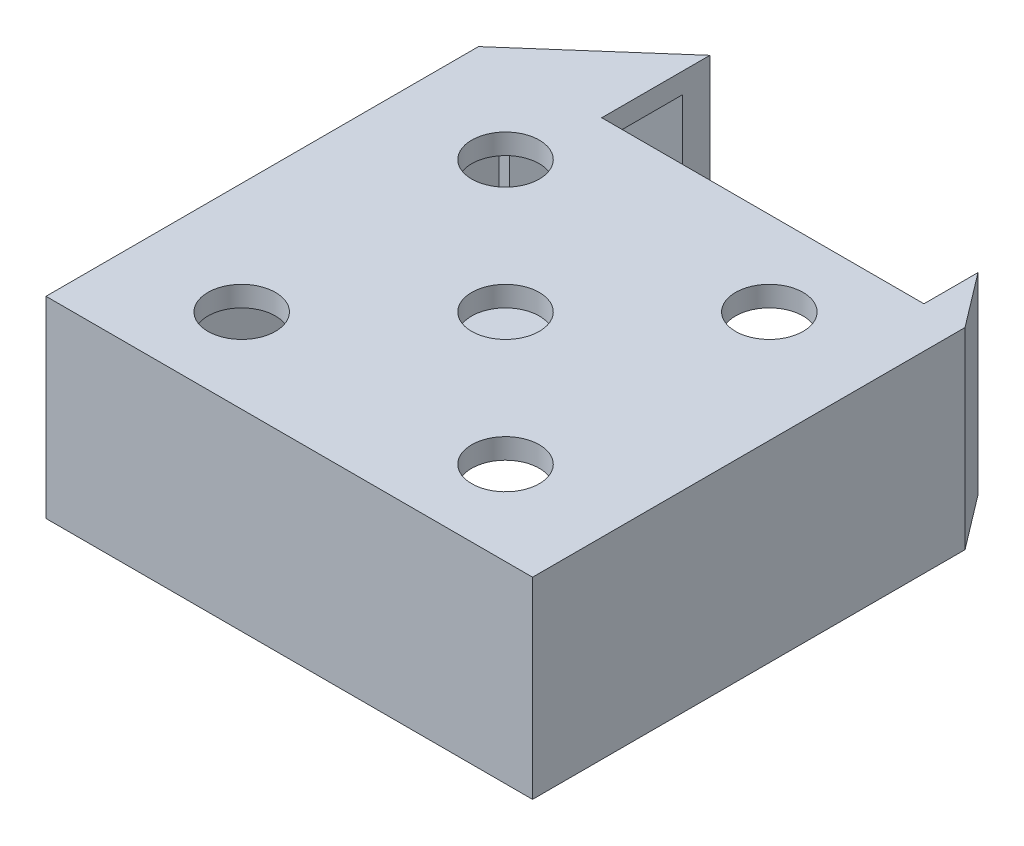
SolidWorks part; units mm, degrees
ref_plane "Front Plane" through (0, 0, 0) normal (0, 0, 1) x (1, 0, 0)
ref_plane "Top Plane" through (0, 0, 0) normal (0, 1, 0) x (1, 0, 0)
ref_plane "Right Plane" through (0, 0, 0) normal (1, 0, 0) x (0, 0, -1)
sketch "Sketch1" plane through (0, 0, 0) normal (0, 1, 0) x (1, 0, 0)
  line L1 (-28.575, 25.4) -> (28.575, 25.4)
  line L2 (-28.575, 25.4) -> (-28.575, -25.4)
  line L3 (-28.575, -25.4) -> (28.575, -25.4)
  line L4 (28.575, 25.4) -> (28.575, -25.4)
  point P4 (0, -25.4)
  point P6 (-28.575, 0)
  dimension "D1" = 57.15
  dimension "D2" = 50.8
extrude "Boss-Extrude1" add sketch "Sketch1" along normal mid plane 22.606
sketch "Sketch2" plane through (0, 0, -25.4) normal (0, 0, -1) x (-1, 0, 0)
  line L0 (-28.575, 11.303) -> (28.575, 11.303) construction
  line L1 (-26.175, 8.903) -> (26.175, 8.903)
  line L2 (-26.175, 8.903) -> (-26.175, -8.903)
  line L3 (-26.175, -8.903) -> (26.175, -8.903)
  line L4 (26.175, 8.903) -> (26.175, -8.903)
  line L5 (-28.575, 11.303) -> (-28.575, -11.303) construction
  point P4 (0, -8.903)
  point P6 (-26.175, 0)
  dimension "D1" = 2.4
  dimension "D2" = 2.4
extrude "Cut-Extrude1" cut sketch "Sketch2" against normal offset from surface (48.514 mm away) 2.286 up to face at (0, 0, 25.4)
sketch "Sketch3" plane through (0, -11.303, 0) normal (0, -1, 0) x (1, 0, 0)
  line L1 (15.494, -15.494) -> (-15.494, -15.494) construction
  line L2 (15.494, -15.494) -> (15.494, 15.494) construction
  line L3 (15.494, 15.494) -> (-15.494, 15.494) construction
  line L4 (-15.494, -15.494) -> (-15.494, 15.494) construction
  line L5 (15.494, -15.494) -> (-15.494, 15.494) construction
  line L6 (15.494, 15.494) -> (-15.494, -15.494) construction
  circle A0 centre (-15.494, 15.494) radius 2.032
  circle A1 centre (15.494, 15.494) radius 2.032
  circle A2 centre (15.494, -15.494) radius 2.032
  circle A3 centre (-15.494, -15.494) radius 2.032
  circle A4 centre (0, 0) radius 11.1125
  point P0 (0, 0)
  point P6 (0, 15.494)
  point P7 (-15.494, 0)
  dimension "D2" = 4.064
  dimension "D3" = 22.225
  dimension "D1" = 30.988
extrude "Cut-Extrude2" cut sketch "Sketch3" against normal up to surface (2.4 mm away) up to face at (0, -8.903, -1.143)
sketch "Sketch4" plane through (0, 11.303, 0) normal (0, 1, 0) x (1, 0, 0)
  circle A0 centre (-15.494, -15.494) radius 2.032 construction
  circle A1 centre (-15.494, 15.494) radius 2.032 construction
  circle A2 centre (15.494, 15.494) radius 2.032 construction
  circle A3 centre (15.494, -15.494) radius 2.032 construction
  circle A4 centre (-15.494, -15.494) radius 2.032 construction
  circle A5 centre (-15.494, 15.494) radius 2.032 construction
  circle A6 centre (15.494, 15.494) radius 2.032 construction
  circle A7 centre (15.494, -15.494) radius 2.032 construction
  circle A8 centre (-15.494, 15.494) radius 3.9687
  circle A9 centre (15.494, 15.494) radius 3.9688
  circle A10 centre (15.494, -15.494) radius 3.9688
  circle A11 centre (-15.494, -15.494) radius 3.9687
  circle A12 centre (0, 0) radius 3.9688
  dimension "D1" = 7.9375
extrude "Cut-Extrude3" cut sketch "Sketch4" against normal up to surface (2.4 mm away) up to face at (0, 8.903, -1.143)
sketch "Sketch5" plane through (0, 11.303, 0) normal (0, 1, 0) x (1, 0, 0)
  line L0 (-28.575, 25.4) -> (-14.097, 25.4)
  line L1 (28.575, 25.4) -> (-28.575, 25.4) construction
  line L2 (-14.097, 25.4) -> (-14.097, 38.1)
  line L3 (-14.097, 38.1) -> (-28.575, 25.4)
  line L4 (28.575, 25.4) -> (23.749, 25.4)
  line L5 (28.575, 25.4) -> (23.749, 31.75)
  line L6 (23.749, 31.75) -> (23.749, 25.4)
  dimension "D1" = 14.478
  dimension "D2" = 12.7
  dimension "D3" = 4.826
  dimension "D4" = 6.35
extrude "Boss-Extrude2" add sketch "Sketch5" against normal up to surface (22.606 mm away) up to face at (0, -11.303, -11.1125)
shell "Shell1" thickness 2.4 removed face at (-20.136, 0, -25.4) removed face at (-14.097, 0, -29.6333)
shell "Shell2" thickness 2.4 removed face at (24.962, 0, -25.4) removed face at (23.749, 0, -27.5167)
equation "\"extrusion_width\"= 0.4mm"
equation "\"shell_num\"= 3"
equation "\"shell_width\"= \"extrusion_width\" * \"shell_num\" * 2"
equation "\"D1@Sketch2\"=\"shell_width\""
equation "\"D2@Sketch2\"=\"shell_width\""
equation "\"D1@Shell1\"=\"shell_width\""
equation "\"D1@Shell2\"=\"shell_width\""
